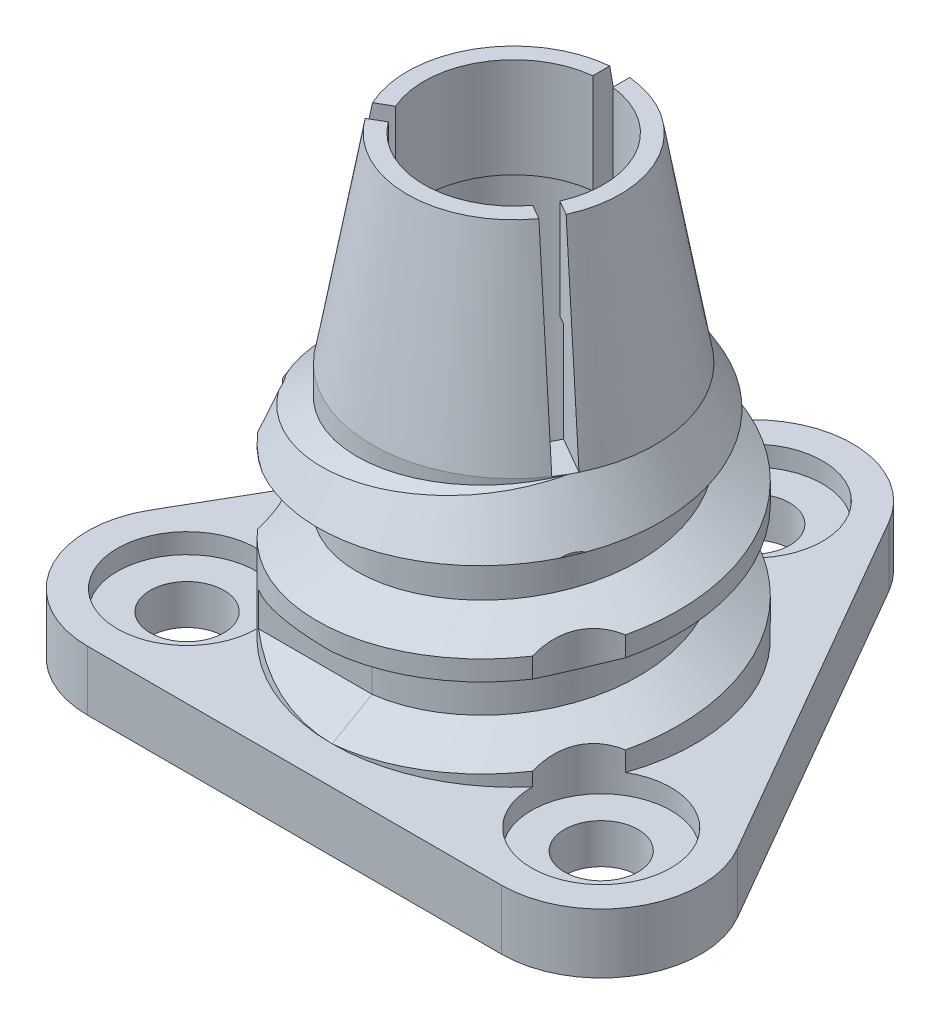
SolidWorks part; units mm, degrees
ref_plane "Front Plane" through (0, 0, 0) normal (0, 0, 1) x (1, 0, 0)
ref_plane "Top Plane" through (0, 0, 0) normal (0, 1, 0) x (1, 0, 0)
ref_plane "Right Plane" through (0, 0, 0) normal (1, 0, 0) x (0, 0, -1)
sketch "Sketch1" plane through (0, 0, 0) normal (0, 1, 0) x (1, 0, 0)
  line L0 (4.3301, 14.5) -> (14.7224, -3.5)
  line L1 (10.3923, -11) -> (-10.3923, -11)
  line L2 (-14.7224, -3.5) -> (-4.3301, 14.5)
  circle A0 centre (0, 0) radius 5.5
  circle A1 centre (0, 12) radius 1.85
  arc A2 (4.3301, 14.5) -> (-4.3301, 14.5) centre (0, 12) ccw
  circle A3 centre (10.3923, -6) radius 1.85
  arc A4 (10.3923, -11) -> (14.7224, -3.5) centre (10.3923, -6) ccw
  circle A5 centre (-10.3923, -6) radius 1.85
  arc A6 (-14.7224, -3.5) -> (-10.3923, -11) centre (-10.3923, -6) ccw
  dimension "D1" = 11
  dimension "D3" = 3.7
  dimension "D4" = 10
  dimension "D2" = 12
  dimension "D5" = 3
extrude "Boss-Extrude1" add sketch "Sketch1" along normal blind 3
sketch "Sketch2" plane through (0, 3, 0) normal (0, 1, 0) x (1, 0, 0)
  circle A0 centre (0, 0) radius 9.1073
extrude "Boss-Extrude2" add sketch "Sketch2" along normal blind 12
sketch "Sketch7" plane through (0, 15, 0) normal (0, 1, 0) x (1, 0, 0)
  circle A0 centre (0, 0) radius 7.1073
extrude "Cut-Extrude2" cut sketch "Sketch7" against normal blind 10 draft 30 flip side to cut
sketch "Sketch3" plane through (0, 15, 0) normal (0, 1, 0) x (1, 0, 0)
  circle A0 centre (0, 0) radius 7.1073
  circle A2 centre (0, 0) radius 9.1073 construction
  dimension "D1" = 2
extrude "Boss-Extrude3" add sketch "Sketch3" along normal blind 10 draft 10
sketch "Sketch4" plane through (0, 25, 0) normal (0, 1, 0) x (1, 0, 0)
  circle A0 centre (0, 0) radius 9.1073 construction
  circle A1 centre (0, 0) radius 9.1073
curve "Helix/Spiral1" pitch 5 height 20 radius 9.1073 centre (0, 25, 0) axis (0, -1, 0) start towards (0, 0, 1)
sketch "Sketch5" plane through (0, 0, 0) normal (1, 0, 0) x (0, 0, -1)
  line L0 (-9.1073, 25) -> (-7.1073, 25) construction
  line L1 (-7.1073, 25.8453) -> (-7.1073, 24.1547)
  line L2 (-7.1073, 24.1547) -> (-9.1073, 23)
  line L4 (-9.1073, 23) -> (-9.1073, 27)
  line L5 (-7.1073, 25.8453) -> (-9.1073, 27)
  spline S1 degree 3 poles (-9.1073, 25) (-9.1073, 24.8965) (-8.6331, 24.6872) (-6.6075, 24.3751) (-3.5759, 24.0625) (0, 23.75) (3.5759, 23.4375) (6.6075, 23.125) (8.6331, 22.8125) (9.3444, 22.5) (8.6331, 22.1875) (6.6075, 21.875) (2.5654, 21.4583) (-2.5654, 21.0417) (-6.6075, 20.625) (-8.6331, 20.3125) (-9.3444, 20) (-8.6331, 19.6875) (-6.6075, 19.375) (-2.5654, 18.9583) (2.5654, 18.5417) (6.6075, 18.125) (8.6331, 17.8125) (9.3444, 17.5) (8.6331, 17.1875) (6.6075, 16.875) (2.5654, 16.4583) (-2.5654, 16.0417) (-6.6075, 15.625) (-8.6331, 15.3125) (-9.3444, 15) (-8.6331, 14.6875) (-6.6075, 14.375) (-2.5654, 13.9583) (2.5654, 13.5417) (6.6075, 13.125) (8.6331, 12.8125) (9.3444, 12.5) (8.6331, 12.1875) (6.6075, 11.875) (2.5654, 11.4583) (-2.5654, 11.0417) (-6.6075, 10.625) (-8.6331, 10.3125) (-9.3444, 10) (-8.6331, 9.6875) (-6.6075, 9.375) (-2.5654, 8.9583) (2.5654, 8.5417) (6.6075, 8.125) (8.6331, 7.8125) (9.3444, 7.5) (8.6331, 7.1875) (6.6075, 6.875) (3.5759, 6.5625) (0, 6.25) (-3.5759, 5.9375) (-6.6075, 5.6249) (-8.6331, 5.3128) (-9.1073, 5.1035) (-9.1073, 5) knots 0 0 0 0 0.015625 0.03125 0.046875 0.0625 0.078125 0.09375 0.109375 0.125 0.140625 0.15625 0.171875 0.203125 0.21875 0.234375 0.25 0.265625 0.28125 0.296875 0.328125 0.34375 0.359375 0.375 0.390625 0.40625 0.421875 0.453125 0.46875 0.484375 0.5 0.515625 0.53125 0.546875 0.578125 0.59375 0.609375 0.625 0.640625 0.65625 0.671875 0.703125 0.71875 0.734375 0.75 0.765625 0.78125 0.796875 0.828125 0.84375 0.859375 0.875 0.890625 0.90625 0.921875 0.9375 0.953125 0.96875 0.984375 1 1 1 1 construction
  point P9 (0, 0)
  point P12 (0, 0)
  point P13 (0, 0)
  dimension "D1" = 30
  dimension "D2" = 4
  dimension "D3" = 2
sweep "Cut-Sweep1" cut profiles "Sketch5" path "Helix/Spiral1" align with end faces yes
sketch "Sketch6" plane through (0, 25, 0) normal (0, 1, 0) x (1, 0, 0)
  circle A0 centre (0, 0) radius 4.5
  dimension "D1" = 9
extrude "Cut-Extrude1" cut sketch "Sketch6" against normal through all
sketch "Sketch8" plane through (0, 0, 0) normal (1, 0, 0) x (0, 0, -1)
  line L4 (-7.1073, 4.1547) -> (-7.1073, 5.8453)
  line L5 (-7.1073, 5.8453) -> (-9.1073, 7)
  line L6 (-9.1073, 7) -> (-9.1073, 3)
  line L7 (-9.1073, 3) -> (-7.1073, 4.1547)
  line L8 (-7.1073, 4.1547) -> (-7.1073, 5.8453)
  line L9 (-7.1073, 5.8453) -> (-9.1073, 7)
  line L10 (-9.1073, 7) -> (-9.1073, 3)
  line L11 (-9.1073, 3) -> (-7.1073, 4.1547)
  dimension "D1" = 0
extrude "Cut-Extrude3" cut sketch "Sketch8" against normal blind 10
sketch "Sketch9" plane through (0, 25, 0) normal (0, 1, 0) x (1, 0, 0)
  line L0 (0, 0) -> (0, 15.6633) construction
  line L1 (0.5, 14.5042) -> (-0.5, 14.5042)
  line L2 (-0.5, 14.5042) -> (-0.5, 1.911)
  line L3 (-0.5, 1.911) -> (0.5, 1.911)
  line L4 (0.5, 14.5042) -> (0.5, 1.911)
  line L5 (12.811, -6.8191) -> (1.905, -0.5225)
  line L6 (12.311, -7.6851) -> (12.811, -6.8191)
  line L7 (12.311, -7.6851) -> (1.405, -1.3885)
  line L8 (1.905, -0.5225) -> (1.405, -1.3885)
  line L9 (-12.311, -7.6851) -> (-1.405, -1.3885)
  line L10 (-12.811, -6.8191) -> (-12.311, -7.6851)
  line L11 (-12.811, -6.8191) -> (-1.905, -0.5225)
  line L12 (-1.405, -1.3885) -> (-1.905, -0.5225)
  point P8 (0, 1.911)
  point P9 (0, 14.5042)
  dimension "D1" = 1
  dimension "D2" = 3
extrude "Cut-Extrude5" cut sketch "Sketch9" against normal up to vertex (51.9989 mm away) up to point (6.2089, 15, 3.4587)
sketch "Sketch10" plane through (0, 0, 0) normal (0, -1, 0) x (1, 0, 0)
  circle A0 centre (0, 0) radius 5
  dimension "D1" = 10
extrude "Cut-Extrude6" cut sketch "Sketch10" against normal offset from surface (20 mm away) 5 up to face at (0, 25, 3.9016)
sketch "Sketch11" plane through (0, 3, 0) normal (0, 1, 0) x (1, 0, 0)
  circle A0 centre (0, 12) radius 3.5
  circle A1 centre (10.3923, -6) radius 3.5
  circle A2 centre (-10.3923, -6) radius 3.5
  dimension "D1" = 7
extrude "Cut-Extrude7" cut sketch "Sketch11" against normal blind 1 and the other way through all
